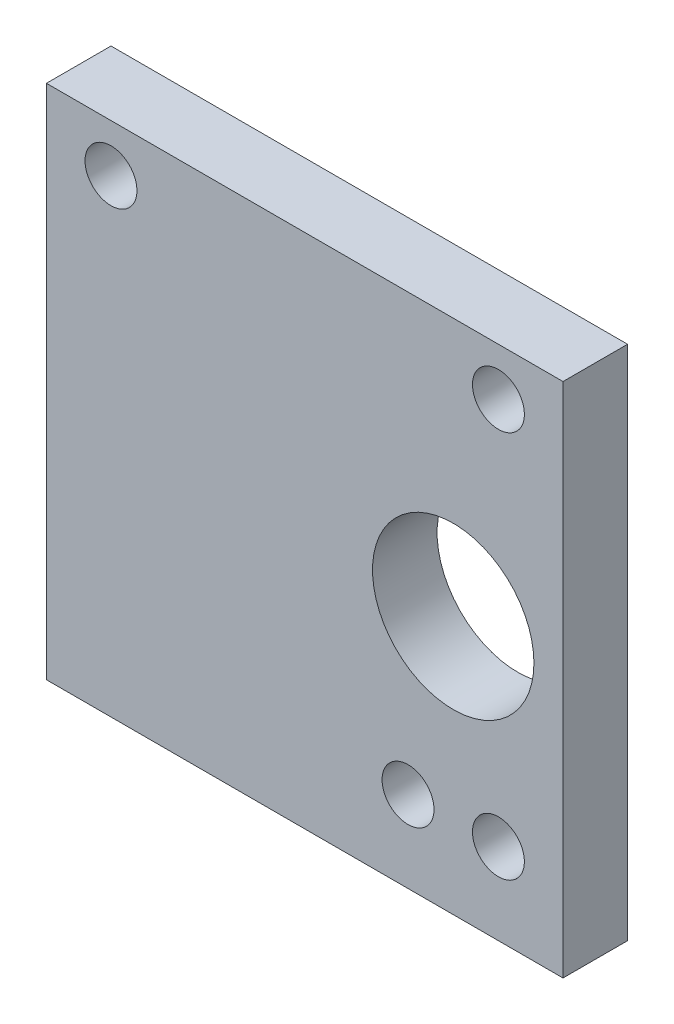
SolidWorks part; units mm, degrees
material "1060 Alloy"
ref_plane "Front Plane" through (0, 0, 0) normal (0, 0, 1) x (1, 0, 0)
ref_plane "Top Plane" through (0, 0, 0) normal (0, 1, 0) x (1, 0, 0)
ref_plane "Right Plane" through (0, 0, 0) normal (1, 0, 0) x (0, 0, -1)
sketch "Sketch1" plane through (0, 0, 0) normal (0, 0, 1) x (1, 0, 0)
  line L0 (0, 25.4) -> (0, -25.4) construction
  line L1 (-25.4, -25.4) -> (25.4, -25.4)
  line L2 (-25.4, -25.4) -> (-25.4, 25.4)
  line L3 (-25.4, 25.4) -> (25.4, 25.4)
  line L4 (25.4, -25.4) -> (25.4, 25.4)
  line L5 (-25.4, -25.4) -> (25.4, 25.4) construction
  line L6 (-25.4, 25.4) -> (25.4, -25.4) construction
  line L7 (25.4, 0) -> (-25.4, 0) construction
  circle A0 centre (-19.05, 20.701) radius 2.5527
  circle A1 centre (19.05, 20.701) radius 2.5527
  circle A2 centre (19.05, -17.399) radius 2.5527
  circle A3 centre (10.16, -17.399) radius 2.5527
  circle A4 centre (14.605, 0) radius 7.9375
  point P0 (0, 0)
  dimension "D3" = 5.1054
  dimension "D7" = 15.875
  dimension "D1" = 50.8
  dimension "D2" = 50.8
  dimension "D4" = 19.05
  dimension "D5" = 20.701
  dimension "D6" = 4.445
  dimension "D8" = 38.1
  dimension "D9" = 8.89
extrude "Boss-Extrude1" add sketch "Sketch1" along normal blind 6.35
